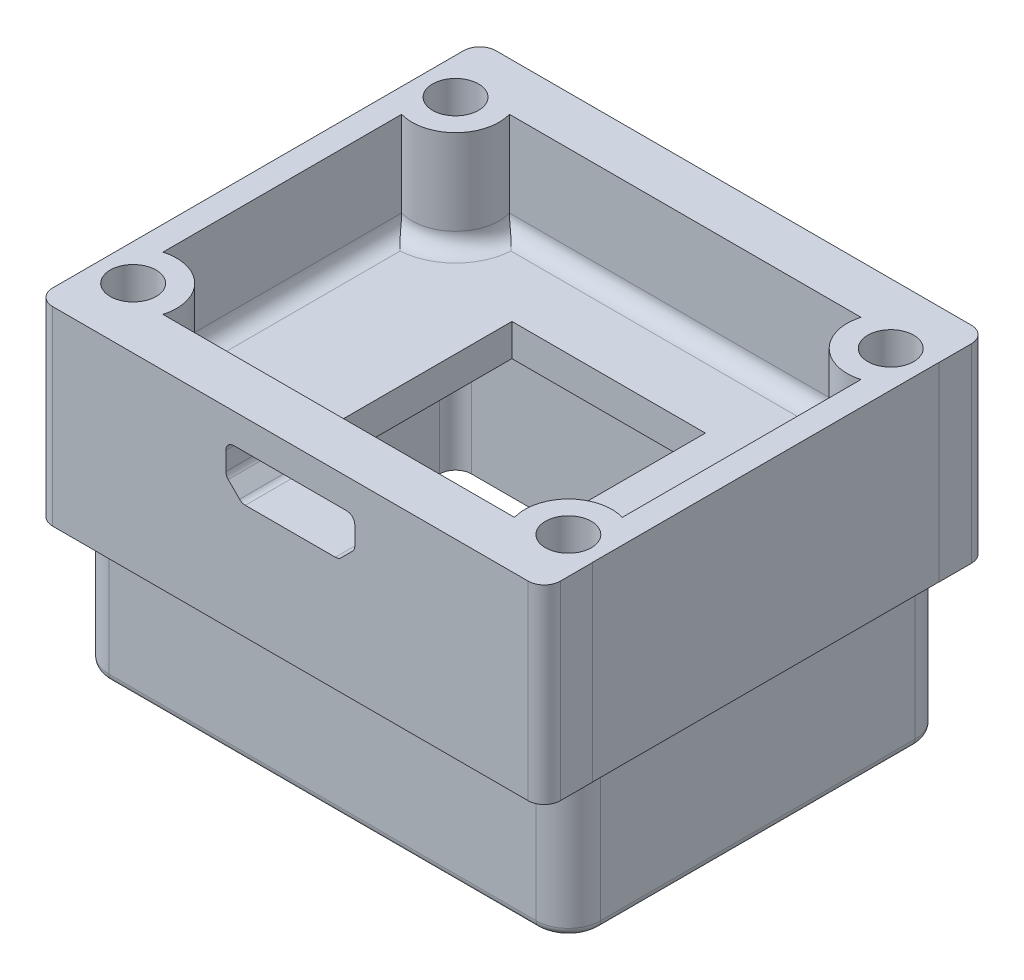
SolidWorks part; units mm, degrees
ref_plane "前视基准面" through (0, 0, 0) normal (0, 0, 1) x (1, 0, 0)
ref_plane "上视基准面" through (0, 0, 0) normal (0, 1, 0) x (1, 0, 0)
ref_plane "右视基准面" through (0, 0, 0) normal (1, 0, 0) x (0, 0, -1)
other "Configuration Table"
ref_plane "基准面1" through (0, 19.5, 0) normal (0, 1, 0) x (1, 0, 0)
sketch "草图1" plane through (0, 19.5, 0) normal (0, 1, 0) x (1, 0, 0)
  line L0 (-15.7466, 13.75) -> (-15.7466, -13.75)
  line L1 (-15.7466, -13.75) -> (15.7538, -13.75)
  line L2 (15.7538, -13.75) -> (15.7538, 13.75)
  line L3 (15.7538, 13.75) -> (-15.7466, 13.75)
extrude "凸台-拉伸1" add sketch "草图1" against normal blind 18.8
sketch "草图2" plane through (0, 0.7, 0) normal (0, -1, 0) x (1, 0, 0)
  line L0 (15.7538, -10.75) -> (15.7538, 10.75)
  line L1 (15.7538, 10.75) -> (15.7466, 10.75)
  line L2 (15.7466, 10.75) -> (15.7466, -10.75)
  line L3 (15.7466, -10.75) -> (15.7538, -10.75)
extrude "切除-拉伸1" cut sketch "草图2" against normal blind 18.8
sketch "草图3" plane through (0, 0.7, 0) normal (0, -1, 0) x (1, 0, 0)
  line L0 (15.25, -11.75) -> (-15.25, -11.75)
  line L1 (-15.25, -11.75) -> (-15.25, 11.75)
  line L2 (-15.25, 11.75) -> (15.25, 11.75)
  line L3 (15.25, 11.75) -> (15.25, -11.75)
extrude "凸台-拉伸2" add sketch "草图3" along normal blind 1.7
sketch "草图4" plane through (0, -1, 0) normal (0, -1, 0) x (1, 0, 0)
  line L0 (-14.25, 10.75) -> (-14.25, -10.75)
  line L1 (-14.25, -10.75) -> (14.25, -10.75)
  line L2 (14.25, -10.75) -> (14.25, 10.75)
  line L3 (14.25, 10.75) -> (-14.25, 10.75)
extrude "切除-拉伸2" cut sketch "草图4" against normal blind 12.2
sketch "草图5" plane through (0, 11.2, 0) normal (0, -1, 0) x (1, 0, 0)
  line L0 (7.9, -7.9) -> (-7.9, -7.9)
  line L1 (-7.9, -7.9) -> (-7.9, 7.9)
  line L2 (-7.9, 7.9) -> (7.9, 7.9)
  line L3 (7.9, 7.9) -> (7.9, -7.9)
extrude "凸台-拉伸3" add sketch "草图5" along normal blind 0.8
sketch "草图6" plane through (0, 19.5, 0) normal (0, 1, 0) x (-1, 0, 0)
  line L0 (-14.25, 7.4063) -> (-14.25, -7.4063)
  line L1 (-10.9063, -10.75) -> (10.9063, -10.75)
  line L2 (14.25, -7.4063) -> (14.25, 7.4063)
  line L3 (10.9063, 10.75) -> (-10.9063, 10.75)
  arc A0 (-10.9063, 10.75) -> (-14.25, 7.4063) centre (-13.5, 10) cw
  arc A1 (-14.25, -7.4063) -> (-10.9063, -10.75) centre (-13.5, -10) cw
  arc A2 (10.9063, -10.75) -> (14.25, -7.4063) centre (13.5, -10) cw
  arc A3 (14.25, 7.4063) -> (10.9063, 10.75) centre (13.5, 10) cw
extrude "切除-拉伸3" cut sketch "草图6" against normal blind 6.3
sketch "草图7" plane through (0, 10.4, 0) normal (0, -1, 0) x (1, 0, 0)
  line L0 (7.1, -7.1) -> (7.1, 7.1)
  line L1 (7.1, 7.1) -> (-7.1, 7.1)
  line L2 (-7.1, 7.1) -> (-7.1, -7.1)
  line L3 (-7.1, -7.1) -> (7.1, -7.1)
extrude "切除-拉伸4" cut sketch "草图7" against normal blind 0.8
sketch "草图8" plane through (0, 13.2, 0) normal (0, 1, 0) x (-1, 0, 0)
  line L0 (-6, -6) -> (6, -6)
  line L1 (6, -6) -> (6, 6)
  line L2 (6, 6) -> (-6, 6)
  line L3 (-6, 6) -> (-6, -6)
extrude "切除-拉伸5" cut sketch "草图8" against normal through all
sketch "草图9" plane through (0, 0, 13.75) normal (0, 0, 1) x (1, 0, 0)
  line L0 (-4, 17.65) -> (-4, 15.8)
  line L1 (-4, 15.8) -> (-3, 14.8)
  line L2 (-3, 14.8) -> (3, 14.8)
  line L3 (3, 14.8) -> (4, 15.8)
  line L4 (4, 15.8) -> (4, 17.65)
  line L5 (4, 17.65) -> (-4, 17.65)
extrude "切除-拉伸6" cut sketch "草图9" against normal up to next
hole_wizard "M2.5 间隙孔1" positions "草图11" profile "草图10" hole size "M2.5" standard "ANSI Metric"
sketch "草图11" plane through (0, 19.5, 0) normal (0, 1, 0) x (1, 0, 0)
  point P0 (13.5, 10)
  point P1 (13.5, -10)
  point P2 (-13.5, -10)
  point P3 (-13.5, 10)
sketch "草图10" plane through (13.5, 19.5, -10) normal (1, 0, 0) x (0, 0, 1)
  line L0 (0, 0) -> (0, 5.5)
  line L1 (0, 5.5) -> (1.425, 5.5)
  line L2 (1.425, 5.5) -> (1.425, 0)
  line L5 (1.425, 0) -> (0, 0)
  line L10 (0, 5.5) -> (-1.425, 5.5) construction
  line L11 (0, -6.35) -> (0, 107.95) construction
  dimension "孔直径" = 2.85
  dimension "孔深度" = 5.5
  dimension "导头角度" = 180
fillet "圆角1" radius 2 4 edges at (-15.25, -0.15, 11.75) (15.25, -0.15, 11.75) (-15.25, -0.15, -11.75) (15.25, -0.15, -11.75) tangent propagation no
fillet "圆角2" radius 0.5 14 edges at (-14.6642, -1, -11.1642) (-15.25, -1, 0) (0, -1, -11.75) (-14.6642, -1, 11.1642) (14.6642, -1, -11.1642) (0, -1, 11.75) (15.25, -1, 0) (14.6642, -1, 11.1642) (3, 14.8, 12.25) (4, 17.65, 12.25) (-4, 15.8, 12.25) (4, 15.8, 12.25) (-3, 14.8, 12.25) (-4, 17.65, 12.25) tangent propagation no
fillet "圆角3" radius 1 16 edges at (14.25, 5.1, 10.75) (-15.7466, 10.1, -13.75) (-14.25, 13.2, 0) (-11.5908, 13.2, -8.0908) (-11.5908, 13.2, 8.0908) (0, 13.2, -10.75) (0, 13.2, 10.75) (11.5908, 13.2, -8.0908) (11.5908, 13.2, 8.0908) (14.25, 13.2, 0) (-14.25, 5.1, -10.75) (15.7538, 10.1, 13.75) (-15.7466, 10.1, 13.75) (15.7538, 10.1, -13.75) (14.25, 5.1, -10.75) (-14.25, 5.1, 10.75) tangent propagation no
sketch "草图12" plane through (0, 0.7, 0) normal (0, -1, 0) x (1, 0, 0)
  line L0 (15.25, -9.75) -> (15.25, 9.75) construction
  line L1 (-13.25, -11.75) -> (13.25, -11.75) construction
  line L2 (-15.25, 9.75) -> (-15.25, -9.75) construction
  line L3 (-13.25, 11.75) -> (13.25, 11.75) construction
  line L4 (15.25, -9.75) -> (15.25, 9.75)
  line L5 (-13.25, -11.75) -> (13.25, -11.75)
  line L6 (-15.25, 9.75) -> (-15.25, -9.75)
  line L7 (-13.25, 11.75) -> (13.25, 11.75)
  line L8 (-15.7466, 12.75) -> (-15.7466, -12.75)
  line L9 (-14.7466, -13.75) -> (14.7538, -13.75)
  line L10 (15.7538, -12.75) -> (15.7538, -10.75)
  line L11 (15.7538, -10.75) -> (15.7466, -10.75)
  line L12 (15.7466, -10.75) -> (15.7466, 10.75)
  line L13 (15.7466, 10.75) -> (15.7538, 10.75)
  line L14 (15.7538, 10.75) -> (15.7538, 12.75)
  line L15 (14.7538, 13.75) -> (-14.7466, 13.75)
  line L16 (-15.7466, 12.75) -> (-15.7466, -12.75)
  line L17 (-14.7466, -13.75) -> (14.7538, -13.75)
  line L18 (15.7538, -12.75) -> (15.7538, -10.75)
  line L19 (15.7538, -10.75) -> (15.7466, -10.75)
  line L20 (15.7466, -10.75) -> (15.7466, 10.75)
  line L21 (15.7466, 10.75) -> (15.7538, 10.75)
  line L22 (15.7538, 10.75) -> (15.7538, 12.75)
  line L23 (14.7538, 13.75) -> (-14.7466, 13.75)
  arc A0 (15.25, 9.75) -> (13.25, 11.75) centre (13.25, 9.75) ccw construction
  arc A1 (13.25, -11.75) -> (15.25, -9.75) centre (13.25, -9.75) ccw construction
  arc A2 (-15.25, -9.75) -> (-13.25, -11.75) centre (-13.25, -9.75) ccw construction
  arc A3 (-13.25, 11.75) -> (-15.25, 9.75) centre (-13.25, 9.75) ccw construction
  arc A4 (-15.7466, -12.75) -> (-14.7466, -13.75) centre (-14.7466, -12.75) ccw
  arc A5 (14.7538, -13.75) -> (15.7538, -12.75) centre (14.7538, -12.75) ccw
  arc A6 (15.7538, 12.75) -> (14.7538, 13.75) centre (14.7538, 12.75) ccw
  arc A7 (-14.7466, 13.75) -> (-15.7466, 12.75) centre (-14.7466, 12.75) ccw
  arc A8 (-15.7466, -12.75) -> (-14.7466, -13.75) centre (-14.7466, -12.75) ccw
  arc A9 (14.7538, -13.75) -> (15.7538, -12.75) centre (14.7538, -12.75) ccw
  arc A10 (15.7538, 12.75) -> (14.7538, 13.75) centre (14.7538, 12.75) ccw
  arc A11 (-14.7466, 13.75) -> (-15.7466, 12.75) centre (-14.7466, 12.75) ccw
  arc A12 (15.25, 9.75) -> (13.25, 11.75) centre (13.25, 9.75) ccw
  arc A13 (13.25, -11.75) -> (15.25, -9.75) centre (13.25, -9.75) ccw
  arc A14 (-15.25, -9.75) -> (-13.25, -11.75) centre (-13.25, -9.75) ccw
  arc A15 (-13.25, 11.75) -> (-15.25, 9.75) centre (-13.25, 9.75) ccw
  dimension "D1" = 0
extrude "切除-拉伸8" cut sketch "草图12" against normal blind 7
